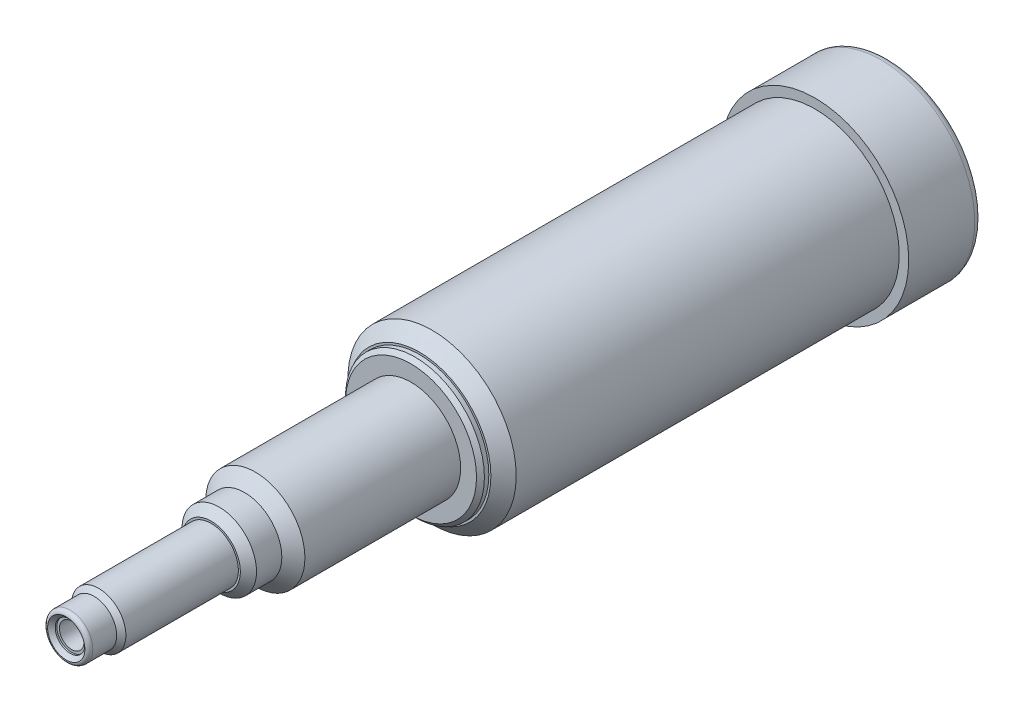
SolidWorks part; units mm, degrees
ref_plane "Front Plane" through (0, 0, 0) normal (0, 0, 1) x (1, 0, 0)
ref_plane "Top Plane" through (0, 0, 0) normal (0, 1, 0) x (1, 0, 0)
ref_plane "Right Plane" through (0, 0, 0) normal (1, 0, 0) x (0, 0, -1)
sketch "Sketch1" plane through (0, 0, 0) normal (1, 0, 0) x (0, 0, -1)
  line L0 (-82.55, 0) -> (82.55, 0) construction
  point P0 (-53.467, 0)
  point P4 (0, 0)
  point P6 (78.994, 0)
  point P7 (67.7164, 0)
  point P8 (-9.144, 0)
  point P9 (-11.684, 0)
  point P10 (-12.573, 0)
  point P11 (-13.3668, 0)
  point P12 (-44.6088, 0)
  point P13 (-46.7678, 0)
  point P14 (-51.8478, 0)
  point P15 (-76.962, 0)
  point P16 (-77.3589, 0)
  point P17 (69.469, 0)
  point P18 (-79.502, 0)
  point P19 (-81.4578, 0)
  dimension "D1" = 132.461
  dimension "Overall Length" = 165.1
  dimension "Nozzle Length" = 29.083
  dimension "D2" = 14.8336
  dimension "D3" = 88.138
  dimension "D4" = 2.54
  dimension "D5" = 0.889
  dimension "D6" = 0.7937
  dimension "D7" = 31.242
  dimension "D8" = 2.159
  dimension "D9" = 5.08
  dimension "D10" = 23.495
  dimension "D11" = 0.3969
  dimension "D12" = 9.525
  dimension "D13" = 3.048
  dimension "D14" = 1.0922
sketch "Sketch2" plane through (0, 0, 0) normal (0, 0, 1) x (1, 0, 0)
  circle A0 centre (0, 0) radius 1.2065 construction
  circle A1 centre (0, 0) radius 2.4638 construction
  circle A2 centre (0, 0) radius 2.9718 construction
  circle A3 centre (0, 0) radius 3.683 construction
  circle A4 centre (0, 0) radius 4.5339 construction
  circle A5 centre (0, 0) radius 5.461 construction
  circle A6 centre (0, 0) radius 7.4803 construction
  circle A7 centre (0, 0) radius 9.9568 construction
  circle A8 centre (0, 0) radius 13.9383 construction
  circle A9 centre (0, 0) radius 16.891 construction
  circle A10 centre (0, 0) radius 18.796 construction
  point P13 (0, 1.2065)
  point P14 (0, 2.4638)
  point P15 (0, 2.9718)
  point P16 (0, 3.683)
  point P17 (0, 4.5339)
  point P18 (0, 5.461)
  point P19 (0, 7.4803)
  point P20 (0, 9.9568)
  point P21 (0, 13.9383)
  point P22 (0, 16.891)
  point P23 (0, 18.796)
  dimension "D1" = 37.592
  dimension "D2" = 27.8765
  dimension "Barrel OD" = 33.782
  dimension "D3" = 19.9136
  dimension "D4" = 14.9606
  dimension "D5" = 10.922
  dimension "D6" = 9.0678
  dimension "D7" = 7.366
  dimension "D8" = 5.9436
  dimension "D9" = 4.9276
  dimension "D10" = 2.413
sketch "Sketch3" plane through (0, 0, 0) normal (1, 0, 0) x (0, 0, -1)
  line L0 (78.994, 16.891) -> (-9.144, 16.891)
  line L1 (-9.144, 16.891) -> (-11.684, 14.351)
  line L2 (-11.684, 14.351) -> (-11.684, 13.9382)
  line L3 (-11.684, 13.9382) -> (-12.573, 13.9382)
  line L4 (-12.573, 13.9382) -> (-13.3668, 13.1445)
  line L5 (-13.3668, 13.1445) -> (-13.3668, 9.9568)
  line L6 (-13.3668, 9.9568) -> (-44.6088, 9.9568)
  line L7 (-44.6088, 9.9568) -> (-46.7678, 7.4803)
  line L8 (-46.7678, 7.4803) -> (-51.8478, 7.4803)
  line L9 (-51.8478, 7.4803) -> (-53.467, 5.8611)
  line L10 (-53.467, 5.8611) -> (-53.467, 5.461)
  line L11 (-53.467, 5.461) -> (-42.8943, 5.461)
  line L12 (-42.8943, 5.461) -> (-42.8943, 8.3693)
  line L13 (-42.8943, 8.3693) -> (-11.7793, 8.3693)
  line L14 (78.994, 16.891) -> (78.994, 15.3035)
  line L15 (78.994, 15.3035) -> (-8.4864, 15.3035)
  line L16 (-8.4864, 15.3035) -> (-10.0965, 13.6934)
  line L17 (-10.0965, 13.6934) -> (-10.0965, 12.3507)
  line L18 (-10.0965, 12.3507) -> (-11.7793, 12.3507)
  line L20 (-11.7793, 12.3507) -> (-11.7793, 8.3693)
  dimension "D1" = 1.5875
  dimension "D2" = 135
  dimension "D3" = 1.7145
  dimension "D4" = 1.5875
  dimension "D5" = 1.5875
  dimension "D6" = 1.5875
  dimension "D7" = 1.5875
  dimension "D8" = 1.5875
revolve "Revolve1" add sketch "Sketch3" angle 360 about L0
sketch "Sketch4" plane through (0, 0, 0) normal (1, 0, 0) x (0, 0, -1)
  line L0 (-42.8943, 8.3693) -> (-41.3068, 8.3693)
  line L2 (-41.3068, 8.3693) -> (-41.3068, 5.461)
  line L3 (-41.3068, 5.461) -> (-32.1496, 4.7895)
  line L4 (-31.7818, 4.3937) -> (-31.7818, 3.175)
  line L5 (-31.7818, 3.175) -> (-41.3068, 3.175)
  line L6 (-41.3068, 3.175) -> (-41.3068, 1.2065)
  line L7 (-41.3068, 1.2065) -> (-69.85, 1.2065)
  line L8 (-69.85, 1.2065) -> (-69.85, 4.5339)
  line L9 (-69.85, 4.5339) -> (-76.962, 4.5339)
  line L10 (-76.962, 4.5339) -> (-76.0349, 5.461)
  line L11 (-76.0349, 5.461) -> (-42.8943, 5.461)
  line L12 (-42.8943, -8.3693) -> (-42.8943, 8.3693) construction
  line L13 (-42.8943, 5.461) -> (-42.8943, 8.3693)
  line L14 (-82.55, 0) -> (82.55, 0) construction
  line L15 (-11.7793, 8.3693) -> (-42.8943, 8.3693) construction
  arc A0 (-32.1496, 4.7895) -> (-31.7818, 4.3937) centre (-32.1786, 4.3937) cw
  point P26 (-31.7818, 4.7625)
  dimension "D7" = 0.3969
  dimension "D1" = 45
  dimension "D2" = 7.112
  dimension "D3" = 1.5875
  dimension "D4" = 4.7625
  dimension "D5" = 1.5875
  dimension "D6" = 9.525
revolve "Revolve2" add sketch "Sketch4" angle 360 about L0
sketch "Sketch5" plane through (0, 0, 0) normal (1, 0, 0) x (0, 0, -1)
  line L0 (-69.85, 4.5339) -> (-69.85, 1.2065)
  line L1 (-69.85, 4.5339) -> (-69.85, -4.5339) construction
  line L2 (-69.85, 1.2065) -> (-77.3589, 1.2065)
  line L3 (-77.3589, 1.2065) -> (-77.3589, 3.683)
  line L4 (-77.3589, 3.683) -> (-81.4578, 3.683)
  line L5 (-81.4578, 3.683) -> (-81.4578, 2.9718)
  line L6 (-81.4578, 2.9718) -> (-81.7816, 2.9718)
  line L7 (-81.7816, 2.9718) -> (-82.55, 3.7401)
  line L8 (-69.85, 4.5339) -> (-81.7563, 4.5339)
  line L9 (-82.55, 0) -> (-82.55, 3.7401) construction
  arc A0 (-81.7563, 4.5339) -> (-82.55, 3.7401) centre (-81.7563, 3.7401) ccw
  dimension "D1" = 0.7937
  dimension "D2" = 135
revolve "Revolve3" add sketch "Sketch5" angle 360 about L0
sketch "Sketch6" plane through (0, 0, 0) normal (1, 0, 0) x (0, 0, -1)
  line L0 (-77.3589, 3.683) -> (-77.3589, -3.683) construction
  line L1 (-81.4578, 3.683) -> (-77.3589, 3.683)
  line L2 (-81.4578, 3.683) -> (-81.4578, 2.4638)
  line L3 (-81.4578, 2.4638) -> (-77.3589, 2.4638)
  line L4 (-77.3589, 3.683) -> (-77.3589, 2.4638)
revolve "Revolve4" add sketch "Sketch6" angle 360 about L0
sketch "Sketch7" plane through (0, 0, 0) normal (1, 0, 0) x (0, 0, -1)
  line L1 (-41.3068, 3.175) -> (-7.9693, 3.175)
  line L2 (-41.3068, 3.175) -> (-41.3068, 1.5875)
  line L3 (-41.3068, 1.5875) -> (-7.9693, 1.5875)
  line L4 (-7.9693, 3.175) -> (-7.9693, 1.5875)
  dimension "D1" = 1.5875
  dimension "D2" = 33.3375
revolve "Revolve5" add sketch "Sketch7" angle 360 about L0
sketch "Sketch8" plane through (0, 0, 0) normal (1, 0, 0) x (0, 0, -1)
  line L0 (-42.8943, 5.461) -> (-53.467, 5.461) construction
  line L1 (-41.3068, 8.3693) -> (-40.513, 8.3693)
  line L2 (-41.3068, 8.3693) -> (-41.3068, 5.461)
  line L3 (-41.3068, 5.461) -> (-40.513, 5.461)
  line L4 (-40.513, 8.3693) -> (-40.513, 5.461)
  dimension "D1" = 0.7937
revolve "Revolve6" add sketch "Sketch8" angle 360 about L0
sketch "Sketch9" plane through (0, 0, 0) normal (1, 0, 0) x (0, 0, -1)
  line L0 (-10.0965, 13.6934) -> (-10.0965, 3.175)
  line L1 (-7.9693, 3.175) -> (-41.3068, 3.175) construction
  line L2 (-10.0965, 3.175) -> (-7.9693, 3.175)
  line L3 (-7.9693, 3.175) -> (-7.9693, 15.3035)
  line L4 (78.994, 15.3035) -> (-8.4864, 15.3035) construction
  line L5 (-7.9693, 15.3035) -> (-8.4864, 15.3035)
  line L6 (-8.4864, 15.3035) -> (-10.0965, 13.6934)
revolve "Revolve7" add sketch "Sketch9" angle 360 about L0
sketch "Sketch10" plane through (0, 0, 0) normal (0, 1, 0) x (0, 0, -1)
  line L0 (-40.513, 5.461) -> (-39.878, 5.461) construction
  line L1 (-40.513, -8.3693) -> (-40.513, 8.3693) construction
  circle A0 centre (-39.878, 6.096) radius 0.635
  dimension "D1" = 1.27
revolve "Revolve8" add sketch "Sketch10" angle 270 about L0 reverse direction yes
ref_plane "Plane1" through (0, 0, 39.878) normal (0, 0, -1) x (-1, 0, 0)
sketch "Sketch11" plane through (0, 0, 39.878) normal (0, 0, -1) x (-1, 0, 0)
  circle A0 centre (0, 0) radius 6.096
  dimension "D1" = 12.192
curve "Helix/Spiral1" pitch 7.2866 height 29.1465 radius 6.096 left hand yes centre (0, 0, 39.878) axis (0, 0, -1) start towards (0, 1, 0)
sketch "Sketch12" plane through (0, 0, 0) normal (-1, 0, 0) x (0, 0, 1)
  circle A0 centre (39.878, 6.096) radius 0.635
  circle A1 centre (39.878, 6.096) radius 0.635 construction
  spline S0 degree 3 poles (39.878, 6.096) (39.7271, 6.096) (39.4221, 5.7786) (38.9673, 4.4227) (38.5117, 2.3936) (38.0564, 0) (37.6009, -2.3936) (37.1455, -4.4227) (36.6901, -5.7786) (36.2347, -6.2547) (35.7793, -5.7786) (35.3239, -4.4227) (34.8684, -2.3936) (34.413, 0) (33.9576, 2.3936) (33.5022, 4.4227) (33.0468, 5.7786) (32.5914, 6.2547) (32.136, 5.7786) (31.6805, 4.4227) (31.2251, 2.3936) (30.7697, 0) (30.3143, -2.3936) (29.8589, -4.4227) (29.4035, -5.7786) (28.9481, -6.2547) (28.4926, -5.7786) (28.0372, -4.4227) (27.5818, -2.3936) (27.1264, 0) (26.671, 2.3936) (26.2156, 4.4227) (25.7602, 5.7786) (25.3048, 6.2547) (24.8493, 5.7786) (24.3939, 4.4227) (23.9385, 2.3936) (23.4831, 0) (23.0277, -2.3936) (22.5723, -4.4227) (22.1169, -5.7786) (21.6614, -6.2547) (21.206, -5.7786) (20.7506, -4.4227) (20.2952, -2.3936) (19.8398, 0) (19.3844, 2.3936) (18.929, 4.4227) (18.4735, 5.7786) (18.0181, 6.2547) (17.5627, 5.7786) (17.1073, 4.4227) (16.6519, 2.3936) (16.1965, 0) (15.7411, -2.3936) (15.2856, -4.4227) (14.8302, -5.7786) (14.3748, -6.2547) (13.9194, -5.7786) (13.464, -4.4227) (13.0086, -2.3936) (12.5531, 0) (12.0978, 2.3936) (11.6422, 4.4227) (11.1874, 5.7786) (10.8824, 6.096) (10.7315, 6.096) knots 0 0 0 0 0.015625 0.03125 0.046875 0.0625 0.078125 0.09375 0.109375 0.125 0.140625 0.15625 0.171875 0.1875 0.203125 0.21875 0.234375 0.25 0.265625 0.28125 0.296875 0.3125 0.328125 0.34375 0.359375 0.375 0.390625 0.40625 0.421875 0.4375 0.453125 0.46875 0.484375 0.5 0.515625 0.53125 0.546875 0.5625 0.578125 0.59375 0.609375 0.625 0.640625 0.65625 0.671875 0.6875 0.703125 0.71875 0.734375 0.75 0.765625 0.78125 0.796875 0.8125 0.828125 0.84375 0.859375 0.875 0.890625 0.90625 0.921875 0.9375 0.953125 0.96875 0.984375 1 1 1 1 construction
sweep "Sweep1" add profiles "Sketch12" path "Helix/Spiral1"
sketch "Sketch13" plane through (0, 0, 0) normal (-1, 0, 0) x (0, 0, 1)
  circle A0 centre (10.7315, 6.096) radius 0.635
  circle A1 centre (10.7315, 6.096) radius 0.635 construction
revolve "Revolve10" add sketch "Sketch13" angle 270 about L0 reverse direction yes
sketch "Sketch14" plane through (0, 0, 0) normal (1, 0, 0) x (0, 0, -1)
  line L0 (69.469, 0) -> (70.485, 0)
  line L1 (-82.55, 0) -> (82.55, 0) construction
  line L2 (70.485, 0) -> (70.485, 14.2875)
  line L3 (70.485, 14.2875) -> (78.994, 14.2875)
  line L4 (78.994, -16.891) -> (78.994, 16.891) construction
  line L5 (78.994, 14.2875) -> (78.994, 15.3035)
  line L6 (78.994, 15.3035) -> (69.469, 15.3035)
  line L7 (78.994, 15.3035) -> (-8.4864, 15.3035) construction
  line L8 (69.469, 15.3035) -> (69.469, 0)
  dimension "D1" = 1.016
revolve "Revolve11" add sketch "Sketch14" angle 360 about L0
sketch "Sketch15" plane through (0, 0, 0) normal (1, 0, 0) x (0, 0, -1)
  line L0 (67.7164, 16.891) -> (67.7164, 18.796)
  line L1 (78.994, 16.891) -> (-9.144, 16.891) construction
  line L2 (67.7164, 18.796) -> (80.9625, 18.796)
  line L3 (82.55, 17.2085) -> (82.55, 0)
  line L4 (82.55, 0) -> (78.994, 0)
  line L5 (78.994, 0) -> (78.994, 16.891)
  line L6 (78.994, 16.891) -> (67.7164, 16.891)
  arc A0 (80.9625, 18.796) -> (82.55, 17.2085) centre (80.9625, 17.2085) cw
  dimension "D1" = 1.5875
revolve "Revolve12" add sketch "Sketch15" angle 360 about L0
